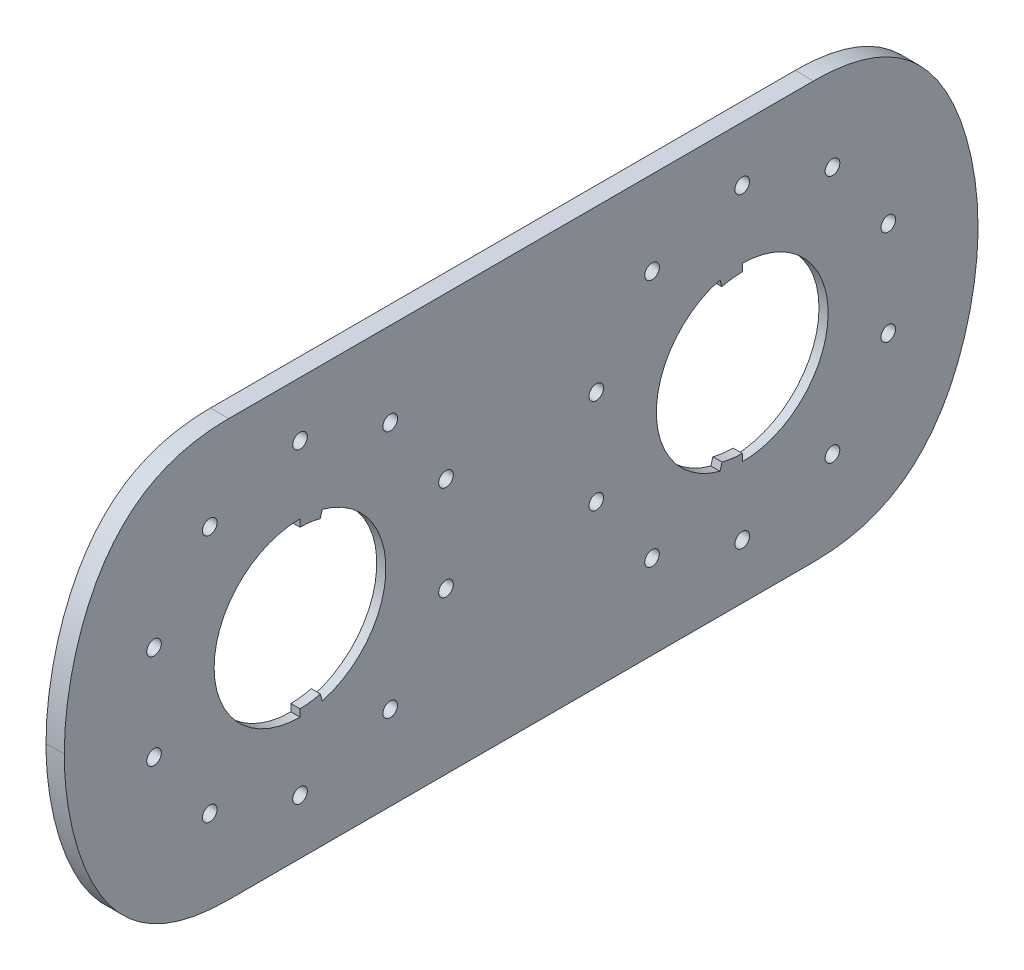
SolidWorks part; units mm, degrees
ref_plane "前视基准面" through (0, 0, 0) normal (0, 0, 1) x (1, 0, 0)
ref_plane "上视基准面" through (0, 0, 0) normal (0, 1, 0) x (1, 0, 0)
ref_plane "右视基准面" through (0, 0, 0) normal (1, 0, 0) x (0, 0, -1)
sketch "草图1" plane through (0, 0, 0) normal (1, 0, 0) x (0, 0, -1)
  line L0 (0, 57) -> (80, 57)
  line L1 (80, -57) -> (0, -57)
  line L2 (0, 57) -> (0, -57)
  line L3 (80, 57) -> (110.7152, 57) construction
  line L4 (110.7152, 57) -> (118.0231, 36.993) construction
  line L5 (118.0231, 36.993) -> (125, 20.498) construction
  line L6 (125, 20.498) -> (125, 0) construction
  line L7 (0, 0) -> (125, 0) construction
  line L8 (80, -57) -> (110.7152, -57) construction
  line L9 (110.7152, -57) -> (118.0231, -36.993) construction
  line L10 (118.0231, -36.993) -> (125, -20.498) construction
  line L11 (125, -20.498) -> (125, 0) construction
  circle A0 centre (60.5, 0) radius 48 construction
  spline S0 degree 4 poles (80, 57) (110.7152, 57) (118.0231, 36.993) (125, 20.498) (125, 0) knots 0 0 0 0 0 1 1 1 1 1
  spline S1 degree 4 poles (80, -57) (110.7152, -57) (118.0231, -36.993) (125, -20.498) (125, 0) knots 0 0 0 0 0 1 1 1 1 1
  dimension "D1" = 60.5
  dimension "D2" = 96
  dimension "D4" = 125
  dimension "D3" = 57
  dimension "D6" = 80
extrude "凸台-拉伸1" add sketch "草图1" along normal blind 5
sketch "草图2" plane through (0, 0, 0) normal (-1, 0, 0) x (0, 0, 1)
  circle A0 centre (-60.5, 0) radius 31
  dimension "D1" = 60.5
  dimension "D2" = 62
extrude "切除-拉伸1" cut sketch "草图2" against normal blind 2.5
sketch "草图3" plane through (0, 0, 0) normal (-1, 0, 0) x (0, 0, 1)
  line L0 (-60.5, 0) -> (-60.5, 79.1647) construction
  line L1 (-60.5, 0) -> (-60.5, 42) construction
  circle A1 centre (-60.5, 42) radius 2
  dimension "D1" = 0
  dimension "D2" = 42
  dimension "D3" = 4
extrude "切除-拉伸2" cut sketch "草图3" against normal up to next
pattern_circular "阵列(圆周)1" count 10 over 360 about axis through (0, 0, -60.5) along (-1, 0, 0) of "切除-拉伸2"
sketch "草图4" plane through (2.5, 0, 0) normal (-1, 0, 0) x (0, 0, 1)
  circle A0 centre (-60.5, 0) radius 23.5
  dimension "D1" = 47
extrude "切除-拉伸3" cut sketch "草图4" against normal up to next
sketch "草图5" plane through (5, 0, 0) normal (1, 0, 0) x (0, 0, -1)
  circle A0 centre (60.5, 0) radius 34.5
  circle A1 centre (60.5, 0) radius 37.5
  dimension "D1" = 75
  dimension "D2" = 69
sketch "草图7" plane through (0, 0, 0) normal (-1, 0, 0) x (0, 0, 1)
  line L0 (-60.5, 48) -> (-81.7662, 48)
  line L1 (-60.5, -48) -> (-81.7662, -48)
  arc A0 (-60.5, 48) -> (-60.5, -48) centre (-60.5, 0) ccw
  arc A1 (-81.7662, 48) -> (-81.7662, -48) centre (-60.5, 0) ccw
  dimension "D1" = 96
  dimension "D2" = 105
sketch "草图8" plane through (5, 0, 0) normal (1, 0, 0) x (0, 0, -1)
  line L0 (54.9354, 20.7674) -> (54.4178, 22.6993)
  line L1 (60.5, 21.5) -> (60.5, 23.5)
  line L2 (60.5, 0) -> (0, 0) construction
  line L3 (60.5, -21.5) -> (60.5, -23.5)
  line L4 (54.9354, -20.7674) -> (54.4178, -22.6993)
  circle A0 centre (60.5, 0) radius 23.5 construction
  arc A1 (60.5, 23.5) -> (54.4178, 22.6993) centre (60.5, 0) ccw
  arc A2 (60.5, 21.5) -> (54.9354, 20.7674) centre (60.5, 0) ccw
  arc A3 (60.5, -21.5) -> (54.9354, -20.7674) centre (60.5, 0) cw
  arc A4 (60.5, -23.5) -> (54.4178, -22.6993) centre (60.5, 0) cw
  dimension "D1" = 43
  dimension "D2" = 15
extrude "凸台-拉伸3" add sketch "草图8" against normal up to surface (2.5 mm away) up to face at (2.5, 0, -37)
mirror "镜向3" about plane through (5, 57, 0) normal (0, 0, -1) of bodies 122 114
sketch "草图9" plane through (5, 0, 0) normal (1, 0, 0) x (0, 0, -1)
  circle A0 centre (0, 0) radius 13.7633
